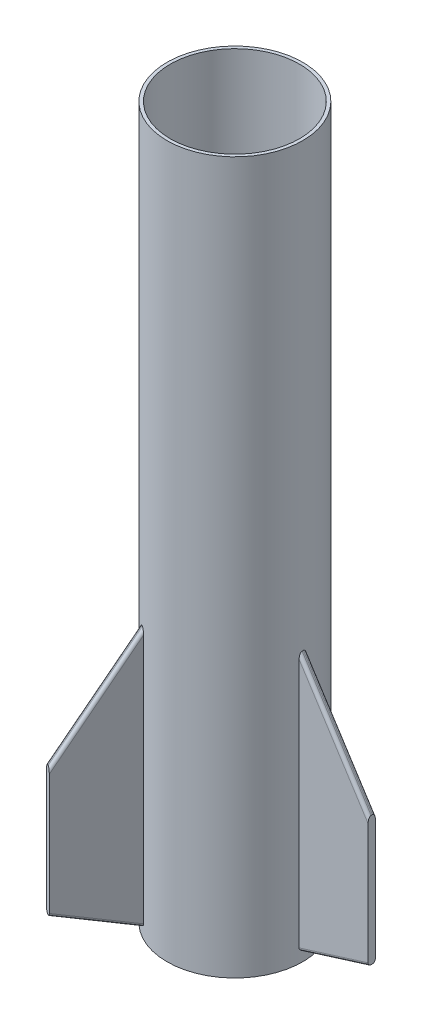
SolidWorks part; units mm, degrees
ref_plane "Front Plane" through (0, 0, 0) normal (0, 0, 1) x (1, 0, 0)
ref_plane "Top Plane" through (0, 0, 0) normal (0, 1, 0) x (1, 0, 0)
ref_plane "Right Plane" through (0, 0, 0) normal (1, 0, 0) x (0, 0, -1)
sketch "Sketch3" plane through (0, 0, 0) normal (0, 1, 0) x (1, 0, 0)
  circle A0 centre (0, 0) radius 40.005
  circle A1 centre (0, 0) radius 38.1
  dimension "D1" = 80.01
  dimension "D2" = 76.2
extrude "Boss-Extrude1" add sketch "Sketch3" along normal blind 419.1
sketch "Sketch4" plane through (0, 0, 0) normal (0, 0, 1) x (1, 0, 0)
  line L0 (40.005, 6.35) -> (40.005, 158.75)
  line L1 (40.005, 0) -> (40.005, 419.1) construction
  line L2 (40.005, 158.75) -> (80.645, 95.25)
  line L3 (80.645, 95.25) -> (80.645, 19.05)
  line L4 (80.645, 19.05) -> (40.005, 6.35)
  dimension "D1" = 76.2
  dimension "D2" = 152.4
  dimension "D3" = 40.64
  dimension "D4" = 12.7
  dimension "D5" = 6.35
extrude "Boss-Extrude2" add sketch "Sketch4" along normal blind 2.159 and the other way blind 2.159 separate body
fillet "Fillet1" radius 1.778 4 edges at (60.325, 12.7, 2.159) (60.325, 12.7, -2.159) (60.325, 127, 2.159) (60.325, 127, -2.159)
sketch "Sketch5" plane through (0, 0, 0) normal (0, 0, 1) x (1, 0, 0)
  line L0 (0, 0) -> (0, 465.0168) construction
pattern_circular "CirPattern1" count 3 over 360 about axis through (0, 0, 0) along (0, 1, 0) reverse direction yes of bodies 102
